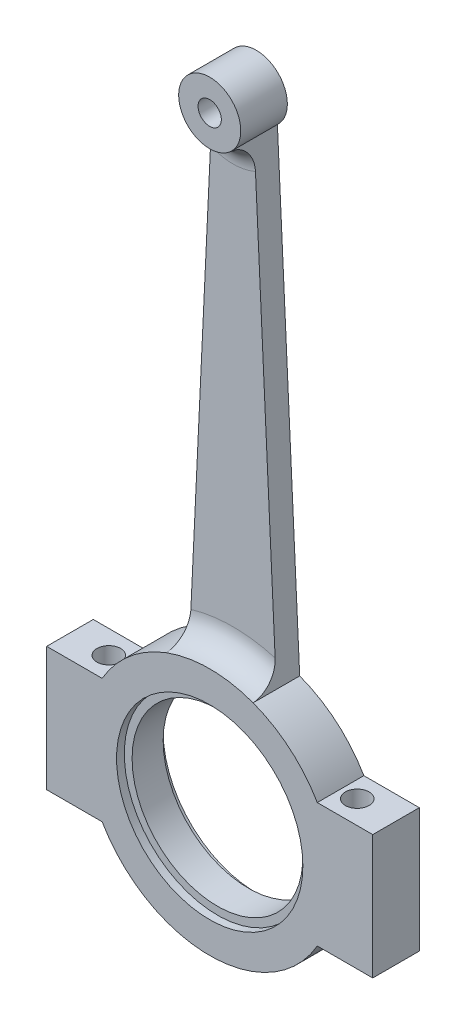
SolidWorks part; units mm, degrees
ref_plane "Front Plane" through (0, 0, 0) normal (0, 0, 1) x (1, 0, 0)
ref_plane "Top Plane" through (0, 0, 0) normal (0, 1, 0) x (1, 0, 0)
ref_plane "Right Plane" through (0, 0, 0) normal (1, 0, 0) x (0, 0, -1)
sketch "Sketch2" plane through (0, 0, 0) normal (0, 0, 1) x (1, 0, 0)
  circle A0 centre (0, 0) radius 2.3813
  circle A1 centre (0, 0) radius 6.35
extrude "Boss-Extrude1" add sketch "Sketch2" along normal blind 9.525
sketch "Sketch4" plane through (0, 0, 0) normal (0, 0, 1) x (1, 0, 0)
  line L0 (0, 7.0119) -> (0, 0) construction
  line L1 (-8.7415, 0) -> (8.394, 0) construction
  line L2 (0, 0) -> (0, -123.825) construction
  line L3 (-25.4, -123.825) -> (-25.4, -111.125) construction
  line L4 (-21.997, -111.125) -> (-33.3375, -111.125)
  line L5 (-33.3375, -111.125) -> (-33.3375, -136.525)
  line L6 (-33.3375, -136.525) -> (-21.997, -136.525)
  line L7 (33.3375, -136.525) -> (21.997, -136.525)
  line L8 (33.3375, -111.125) -> (33.3375, -136.525)
  line L9 (21.997, -111.125) -> (33.3375, -111.125)
  circle A0 centre (0, -123.825) radius 17.4625
  circle A1 centre (0, -123.825) radius 19.05
  arc A2 (-21.997, -136.525) -> (21.997, -136.525) centre (0, -123.825) ccw
  arc A3 (21.997, -111.125) -> (-21.997, -111.125) centre (0, -123.825) ccw
  point P19 (-17.4625, -123.825)
  dimension "D1" = 25.4
  dimension "D2" = 38.1
  dimension "D3" = 34.925
  dimension "D4" = 50.8
extrude "Boss-Extrude2" add sketch "Sketch4" along normal blind 9.525 separate body contours L9 A3 L4 L5 L6 A2 L7 L8 A1 | A1 A0 region at (0, -99.2632, 0) region at (-18.5112, -123.825, 0)
sketch "Sketch6" plane through (0, 0, 9.525) normal (0, 0, 1) x (1, 0, 0)
  circle A0 centre (0, -123.825) radius 19.05 construction
  circle A1 centre (0, -123.825) radius 19.05
extrude "Cut-Extrude1" cut sketch "Sketch6" against normal blind 1.5875
sketch "Sketch7" plane through (0, 0, 0) normal (0, 0, -1) x (-1, 0, 0)
  circle A0 centre (0, -123.825) radius 19.05 construction
  circle A1 centre (0, -123.825) radius 19.05
extrude "Cut-Extrude2" cut sketch "Sketch7" against normal blind 1.5875
hole_wizard "#11 (0.191) Diameter Hole1" positions "Sketch8" profile "Sketch9" hole size "#11" standard "ANSI Inch" end condition through all
sketch "Sketch8" plane through (0, -111.125, 0) normal (0, 1, 0) x (1, 0, 0)
  line L0 (0, -5.2388) -> (0, 5.2388) construction
  point P0 (-25.4, -4.7625)
  point P6 (25.4, -4.7625)
  dimension "D1" = 25.4
sketch "Sketch9" plane through (-25.4, -111.125, 4.7625) normal (1, 0, 0) x (0, 0, 1)
  line L0 (0, 0) -> (0, 38.1)
  line L1 (0, 38.1) -> (2.4257, 38.1)
  line L2 (2.4257, 38.1) -> (2.4257, 0)
  line L5 (2.4257, 0) -> (0, 0)
  line L11 (0, -6.35) -> (0, 107.95) construction
  dimension "Thru Hole Dia." = 4.8514
  dimension "Thru Hole Depth" = 38.1
sketch "Sketch10" plane through (0, 0, 0) normal (0, 0, 1) x (1, 0, 0)
  line L0 (0, 0) -> (0, -123.825) construction
  line L1 (0, 0) -> (0, -123.825) construction
  line L2 (4.3183, -4.6557) -> (8.8748, -100.0259)
  line L3 (-4.3183, -4.6557) -> (-8.8748, -100.0259)
  circle A0 centre (0, 0) radius 6.35 construction
  circle A1 centre (0, 0) radius 6.35
  arc A2 (21.997, -111.125) -> (-21.997, -111.125) centre (0, -123.825) ccw construction
  arc A3 (21.997, -111.125) -> (-21.997, -111.125) centre (0, -123.825) ccw
  point P10 (11.6035, -101.2304)
  point P11 (8.8748, -100.0259)
extrude "Boss-Extrude3" add sketch "Sketch10" along normal blind 4.7625 contours L1 A1 L3 A3 | A1 L1 A3 L2 region at (3.4453, -57.6151, 0) region at (-3.4453, -57.6151, 0)
fillet "Fillet1" radius 5.08 2 edges at (0, -98.425, 4.7625) (0, -6.35, 4.7625)
